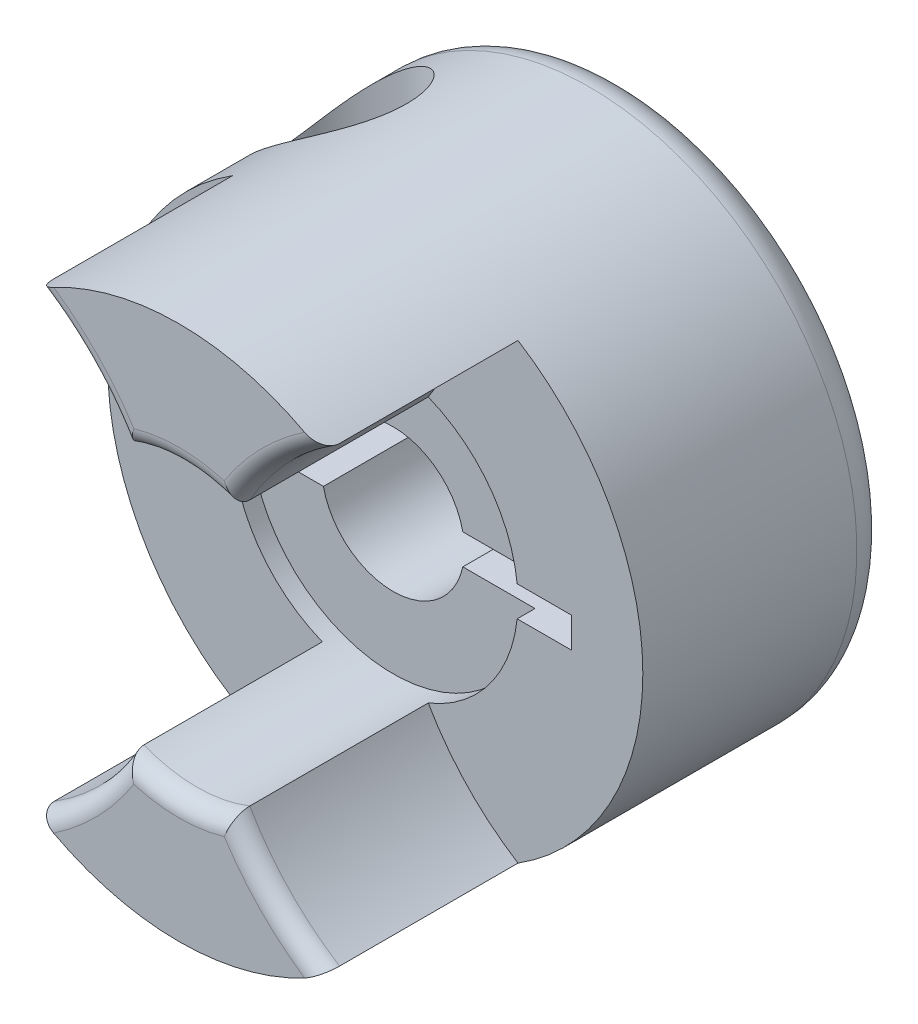
SolidWorks part; units mm, degrees
ref_plane "Front Plane" through (0, 0, 0) normal (0, 0, 1) x (1, 0, 0)
ref_plane "Top Plane" through (0, 0, 0) normal (0, 1, 0) x (1, 0, 0)
ref_plane "Right Plane" through (0, 0, 0) normal (1, 0, 0) x (0, 0, -1)
sketch "Sketch1" plane through (0, 0, 0) normal (0, 0, 1) x (1, 0, 0)
  circle A0 centre (0, 0) radius 15
extrude "Boss-Extrude1" add sketch "Sketch1" along normal blind 25
sketch "Sketch3" plane through (0, 0, 25) normal (0, 0, 1) x (1, 0, 0)
  arc A0 (2.9688, -7.4288) -> (2.9688, 7.4288) centre (16, 0) ccw
  arc A1 (-2.9688, 7.4288) -> (-2.9688, -7.4288) centre (-16, 0) ccw
  arc A2 (2.9688, 7.4288) -> (-2.9688, 7.4288) centre (0, 0) ccw
  arc A3 (-2.9688, -7.4288) -> (2.9688, -7.4288) centre (0, 0) ccw
extrude "Cut-Extrude1" cut sketch "Sketch3" against normal blind 11
sketch "Sketch4" plane through (0, 0, 14) normal (0, 0, 1) x (1, 0, 0)
  circle A0 centre (0, 0) radius 4
  dimension "D1" = 8
extrude "Cut-Extrude2" cut sketch "Sketch4" against normal blind 14
sketch "Sketch5" plane through (0, 0, 14) normal (0, 0, 1) x (1, 0, 0)
  circle A0 centre (0, 0) radius 8
extrude "Cut-Extrude3" cut sketch "Sketch5" against normal blind 1
sketch "Sketch6" plane through (0, 0, 14) normal (0, 0, 1) x (1, 0, 0)
  line L1 (-17.8419, 0.85) -> (11, 0.85)
  line L2 (-17.8419, 0.85) -> (-17.8419, -0.85)
  line L3 (-17.8419, -0.85) -> (11, -0.85)
  line L4 (11, 0.85) -> (11, -0.85)
extrude "Cut-Extrude4" cut sketch "Sketch6" against normal blind 14
sketch "Sketch7" plane through (0, 0, 0) normal (0, 0, -1) x (-1, 0, 0)
  line L1 (-11, 0.85) -> (-3.9086, 0.85)
  line L2 (-11, 0.85) -> (-11, -0.85)
  line L3 (-11, -0.85) -> (-3.9086, -0.85)
  line L4 (-3.9086, 0.85) -> (-3.9086, -0.85)
extrude "Boss-Extrude2" add sketch "Sketch7" against normal blind 2
chamfer "Chamfer1" distance 11 angle 45 1 edges at (11, 0, 2)
sketch "Sketch8" plane through (0, 0, 0) normal (0, 1, 0) x (1, 0, 0)
  circle A0 centre (-9, -7) radius 2
extrude "Cut-Extrude5" cut sketch "Sketch8" against normal blind 14 and the other way blind 14
ref_plane "Plane1" through (0, 15, 0) normal (0, 1, 0) x (1, 0, 0)
sketch "Sketch9" plane through (0, 15, 0) normal (0, 1, 0) x (1, 0, 0)
  circle A0 centre (-9, -7) radius 3.75
extrude "Cut-Extrude6" cut sketch "Sketch9" against normal blind 11
fillet "Fillet1" radius 2 1 edges at (15, 0, 0)
fillet "Fillet2" radius 1 6 edges at (0, -8, 25) (0, 8, 25) (5.1605, 10.3685, 25) (-5.1605, 10.3685, 25) (-5.1605, -10.3685, 25) (5.1605, -10.3685, 25)
